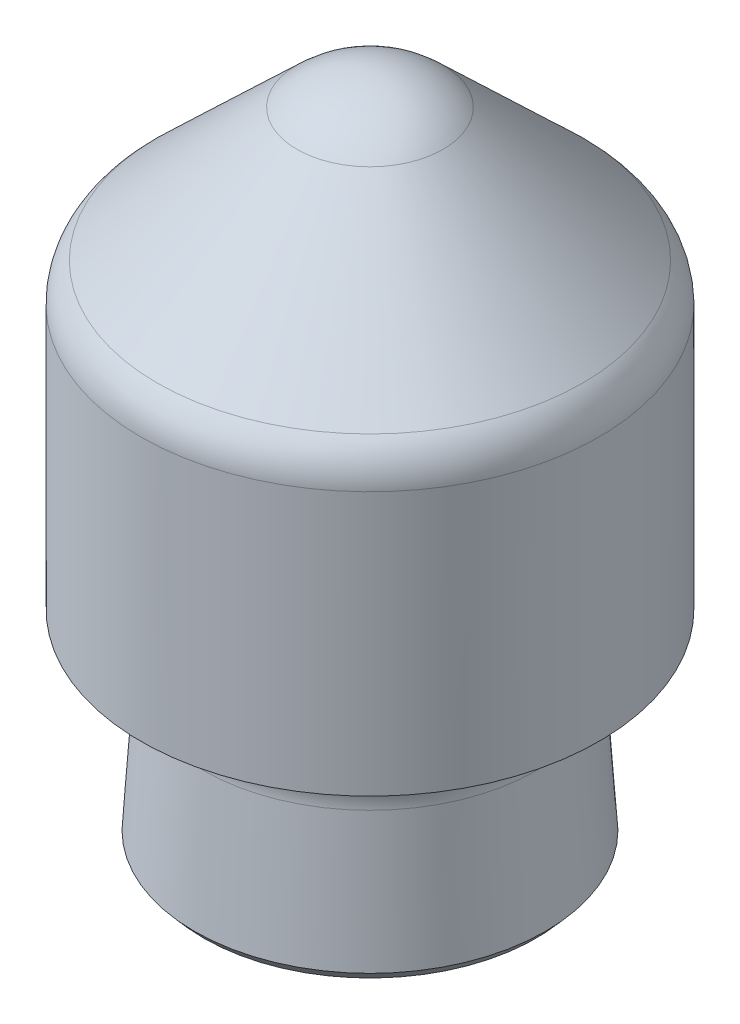
SolidWorks part; units mm, degrees
material "6061-T6 (SS)"
ref_plane "Front Plane" through (0, 0, 0) normal (0, 0, 1) x (1, 0, 0)
ref_plane "Top Plane" through (0, 0, 0) normal (0, 1, 0) x (1, 0, 0)
ref_plane "Right Plane" through (0, 0, 0) normal (1, 0, 0) x (0, 0, -1)
sketch "Sketch1" plane through (0, 0, 0) normal (0, 0, 1) x (1, 0, 0)
  line L0 (0, 25.4) -> (0, 41.3512) construction
  line L2 (4.7085, 14.7066) -> (-4.7085, 14.7066) construction
  line L3 (0, 25.4) -> (-4.2164, 25.4)
  line L4 (-3.899, 30.2387) -> (-4.2164, 25.4)
  line L5 (0, 25.4) -> (0, 41.3512)
  line L6 (-3.899, 30.2387) -> (-5.4864, 30.2387)
  line L7 (-5.4864, 30.2387) -> (-5.4864, 37.0967)
  line L8 (-1.7509, 40.6513) -> (-5.4864, 37.0967)
  arc A0 (-1.7509, 40.6513) -> (0, 41.3512) centre (0, 38.8112) cw
  dimension "D6" = 2.54
  dimension "D1" = 26.6446
  dimension "D2" = 3.899
  dimension "D3" = 10.9728
  dimension "D4" = 4.2545
  dimension "D5" = 11.1125
  dimension "D7" = 1.27
revolve "Revolve1" add sketch "Sketch1" angle 360 about L0
fillet "Fillet1" radius 1.27 1 edges at (0, 37.0967, -5.4864)
fillet "Fillet2" radius 1.27 1 edges at (0, 30.2387, -3.899)
chamfer "Chamfer1" distance 0.254 angle 45 1 edges at (0, 25.4, -4.2164) first distance on face at (0, 28.8856, -3.9878)
sketch "Sketch4" plane through (0, 25.4, 0) normal (0, -1, 0) x (1, 0, 0)
  circle A0 centre (0, 0) radius 3.5
  dimension "D1" = 7
extrude "Cut-Extrude1" cut sketch "Sketch4" against normal blind 2.5
hole_wizard "M7x0.75 Tapped Hole1" positions "Sketch5" profile "Sketch6" tap size "M7x1.0" standard "ANSI Metric"
sketch "Sketch5" plane through (0, 25.4, 0) normal (0, -1, 0) x (-1, 0, 0)
  point P0 (0, 0)
  point P3 (96.1394, -180.6847)
sketch "Sketch6" plane through (0, 25.4, 0) normal (1, 0, 0) x (0, 0, -1)
  line L0 (0, 0) -> (0, 12.7566)
  line L1 (0, 12.7566) -> (3, 10.954)
  line L2 (3, 10.954) -> (3, 0)
  line L5 (3, 0) -> (0, 0)
  line L10 (0, 12.7566) -> (-3, 10.954) construction
  line L11 (0, -6.35) -> (0, 107.95) construction
  dimension "Tap Drill Dia." = 6
  dimension "Tap Drill Depth" = 10.954
  dimension "Drill Angle" = 118
cosmetic thread "Hole Thread1" parameters "D1"=9.906, "D2"=7
